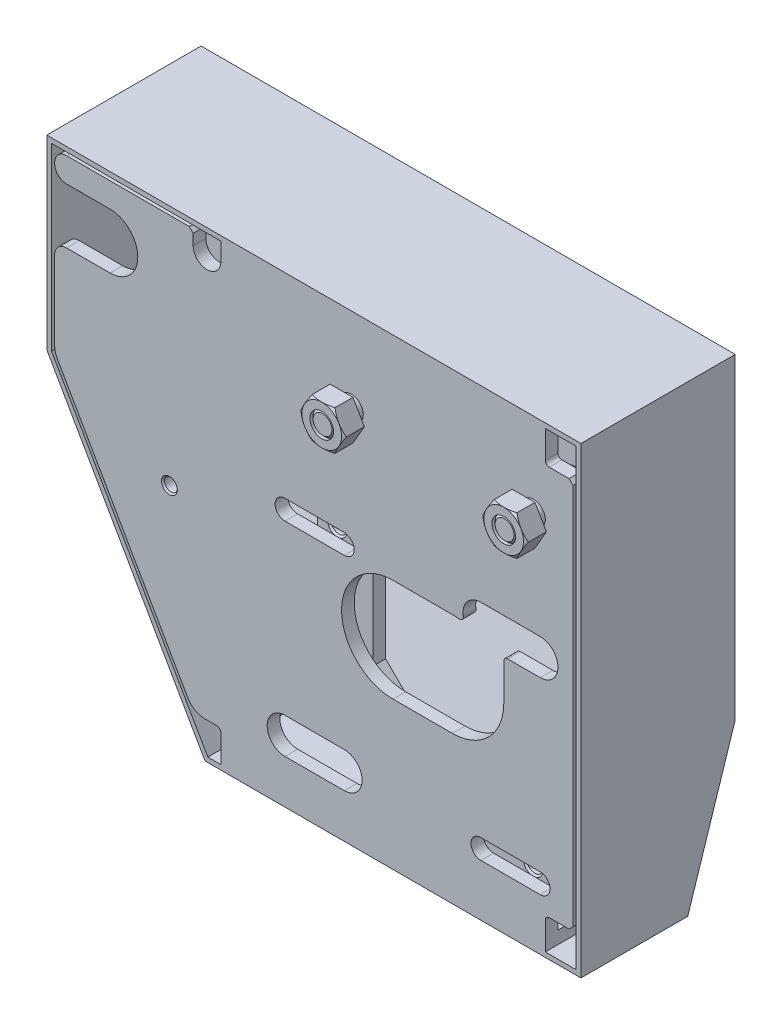
SolidWorks part; units mm, degrees
ref_plane "前视基准面" through (0, 0, 0) normal (0, 0, 1) x (1, 0, 0)
ref_plane "上视基准面" through (0, 0, 0) normal (0, 1, 0) x (1, 0, 0)
ref_plane "右视基准面" through (0, 0, 0) normal (1, 0, 0) x (0, 0, -1)
ref_plane "基准面4" through (0, 0, 0) normal (0, 0, 1) x (1, 0, 0)
sketch "草图1" plane through (0, 0, 0) normal (0, 0, 1) x (1, 0, 0)
  line L0 (-16, 15.2) -> (-16, -101.8)
  line L1 (-16, -101.8) -> (119, -101.8)
  line L2 (119, -101.8) -> (119, 15.2)
  line L3 (119, 15.2) -> (-16, 15.2)
extrude "凸台-拉伸1" add sketch "草图1" against normal blind 39
sketch "草图2" plane through (0, 0, 0) normal (0, 0, 1) x (1, 0, 0)
  line L0 (-14.8, 14) -> (-14.8, -31.4813)
  line L1 (-14.8, -31.4813) -> (24.6964, -100.6)
  line L2 (24.6964, -100.6) -> (117.8, -100.6)
  line L3 (117.8, -100.6) -> (117.8, 14)
  line L4 (117.8, 14) -> (-14.8, 14)
extrude "切除-拉伸1" cut sketch "草图2" against normal blind 37.8
ref_plane "基准面5" through (-16, 0, 0) normal (1, 0, 0) x (0, 0, -1)
sketch "草图3" plane through (-16, 0, 0) normal (1, 0, 0) x (0, 0, -1)
  line L0 (25.7385, -101.8) -> (39, -101.8)
  line L1 (39, -101.8) -> (39, -60.9103)
  line L2 (39, -60.9103) -> (25.7385, -101.8)
extrude "凸台-拉伸2" add sketch "草图3" along normal blind 135
sketch "草图4" plane through (-16, 0, 0) normal (1, 0, 0) x (0, 0, -1)
  line L0 (27, -101.8) -> (39, -101.8)
  line L1 (39, -101.8) -> (39, -64.8)
  line L2 (39, -64.8) -> (27, -101.8)
extrude "切除-拉伸2" cut sketch "草图4" along normal blind 135
ref_plane "基准面6" through (0, 0, 0) normal (0, 0, 1) x (1, 0, 0)
sketch "草图5" plane through (0, 0, 0) normal (0, 0, 1) x (1, 0, 0)
  line L0 (-16, -101.8) -> (24, -101.8)
  line L1 (24, -101.8) -> (-16, -31.8)
  line L2 (-16, -31.8) -> (-16, -101.8)
extrude "切除-拉伸3" cut sketch "草图5" against normal blind 39
ref_plane "基准面7" through (28, 0, 0) normal (1, 0, 0) x (0, 0, -1)
sketch "草图6" plane through (28, 0, 0) normal (1, 0, 0) x (0, 0, -1)
  line L0 (0, 14) -> (0, -100.6)
  line L1 (0, -100.6) -> (18, -100.6)
  line L2 (18, -100.6) -> (18, -97.4)
  line L3 (18, -97.4) -> (3.2, -97.4)
  line L4 (3.2, -97.4) -> (3.2, 10.8)
  line L5 (3.2, 10.8) -> (18, 10.8)
  line L6 (18, 10.8) -> (18, 14)
  line L7 (18, 14) -> (0, 14)
extrude "凸台-拉伸3" add sketch "草图6" along normal blind 82
ref_plane "基准面8" through (0, 0, 0) normal (0, 0, 1) x (1, 0, 0)
sketch "草图7" plane through (0, 0, 0) normal (0, 0, 1) x (1, 0, 0)
  line L0 (-13.3412, -32.4217) -> (19.6068, -90.0807)
  line L1 (23.948, -92.6) -> (27, -92.6)
  line L2 (28, -93.6) -> (28, -100.6)
  line L3 (28, -100.6) -> (110, -100.6)
  line L4 (110, -100.6) -> (110, -93.6)
  line L5 (111, -92.6) -> (116, -92.6)
  line L6 (116, -92.6) -> (117, -91.6)
  line L7 (117, -91.6) -> (117, 5)
  line L8 (117, 5) -> (116, 6)
  line L9 (116, 6) -> (111, 6)
  line L10 (110, 7) -> (110, 14)
  line L11 (110, 14) -> (28, 14)
  line L12 (28, 14) -> (28, 9.5)
  line L13 (21, 9.5) -> (21, 12.2)
  line L14 (21, 12.2) -> (20, 13.2)
  line L15 (20, 13.2) -> (-11, 13.2)
  line L16 (-14, 10.2) -> (-14, 10)
  line L17 (-11, 7) -> (0, 7)
  line L18 (0, -7) -> (-11, -7)
  line L19 (-14, -10) -> (-14, -29.941)
  arc A0 (-14, -29.941) -> (-13.3412, -32.4217) centre (-9, -29.941) ccw
  arc A1 (19.6068, -90.0807) -> (23.948, -92.6) centre (23.948, -87.6) ccw
  arc A2 (27, -92.6) -> (28, -93.6) centre (27, -93.6) cw
  arc A3 (110, -93.6) -> (111, -92.6) centre (111, -93.6) cw
  arc A4 (111, 6) -> (110, 7) centre (111, 7) cw
  arc A5 (28, 9.5) -> (21, 9.5) centre (24.5, 9.5) cw
  arc A6 (-11, 13.2) -> (-14, 10.2) centre (-11, 10.2) ccw
  arc A7 (-14, 10) -> (-11, 7) centre (-11, 10) ccw
  arc A8 (0, 7) -> (0, -7) centre (0, 0) cw
  arc A9 (-11, -7) -> (-14, -10) centre (-11, -10) ccw
extrude "凸台-拉伸4" add sketch "草图7" against normal blind 3.2
ref_plane "基准面9" through (0, 0, 0) normal (0, 0, 1) x (1, 0, 0)
sketch "草图8" plane through (0, 0, 0) normal (0, 0, 1) x (1, 0, 0)
  line L0 (71.5, -64.5) -> (86.5, -64.5)
  line L1 (99.5, -51.5) -> (99.5, -42.2)
  line L2 (100.5, -41.2) -> (108.7, -41.2)
  line L3 (108.7, -32.2) -> (93.7, -32.2)
  line L4 (86.5, -38.5) -> (71.5, -38.5)
  arc A0 (71.5, -38.5) -> (71.5, -64.5) centre (71.5, -51.5) ccw
  arc A1 (86.5, -64.5) -> (99.5, -51.5) centre (86.5, -51.5) ccw
  arc A2 (99.5, -42.2) -> (100.5, -41.2) centre (100.5, -42.2) cw
  arc A3 (108.7, -41.2) -> (108.7, -32.2) centre (108.7, -36.7) ccw
  arc A4 (93.7, -32.2) -> (89.2625, -37.4471) centre (93.7, -36.7) ccw
  arc A5 (89.2625, -37.4471) -> (88.1495, -38.6051) centre (88.2763, -37.6131) cw
  arc A6 (88.1495, -38.6051) -> (86.5, -38.5) centre (86.5, -51.5) ccw
extrude "切除-拉伸4" cut sketch "草图8" against normal blind 3.2
sketch "草图9" plane through (0, 0, 0) normal (0, 0, 1) x (1, 0, 0)
  line L0 (44.2, -90.7) -> (59.2, -90.7)
  line L1 (59.2, -81.7) -> (44.2, -81.7)
  arc A0 (44.2, -81.7) -> (44.2, -90.7) centre (44.2, -86.2) ccw
  arc A1 (59.2, -90.7) -> (59.2, -81.7) centre (59.2, -86.2) ccw
extrude "切除-拉伸5" cut sketch "草图9" against normal blind 3.2
sketch "草图10" plane through (0, 0, 0) normal (0, 0, 1) x (1, 0, 0)
  line L0 (44.2, -39.2) -> (59.2, -39.2)
  line L1 (59.2, -34.2) -> (44.2, -34.2)
  arc A0 (44.2, -34.2) -> (44.2, -39.2) centre (44.2, -36.7) ccw
  arc A1 (59.2, -39.2) -> (59.2, -34.2) centre (59.2, -36.7) ccw
extrude "切除-拉伸6" cut sketch "草图10" against normal blind 3.2
sketch "草图11" plane through (0, 0, 0) normal (0, 0, 1) x (1, 0, 0)
  line L0 (93.7, -88.7) -> (108.7, -88.7)
  line L1 (108.7, -83.7) -> (93.7, -83.7)
  arc A0 (93.7, -83.7) -> (93.7, -88.7) centre (93.7, -86.2) ccw
  arc A1 (108.7, -88.7) -> (108.7, -83.7) centre (108.7, -86.2) ccw
extrude "切除-拉伸7" cut sketch "草图11" against normal blind 3.2
ref_plane "基准面10" through (15, 0, 0) normal (1, 0, 0) x (0, 0, -1)
sketch "草图12" plane through (15, 0, 0) normal (1, 0, 0) x (0, 0, -1)
  line L0 (0, -46) -> (0, -44)
  line L1 (0, -44) -> (0.379, -44.379)
  line L2 (0.379, -44.379) -> (2.821, -44.379)
  line L3 (2.821, -44.379) -> (3.2, -44)
  line L4 (3.2, -44) -> (3.2, -46)
  line L5 (3.2, -46) -> (0, -46)
  line L6 (3.2, -46) -> (0, -46) construction
revolve "切除-旋转1" cut sketch "草图12" angle 360 about L6 reverse direction yes
cosmetic thread "装饰螺纹线1" parameters "D1"=3.2, "D2"=4
ref_plane "基准面11" through (0, -6, 0) normal (0, 1, 0) x (1, 0, 0)
sketch "草图13" plane through (0, -6, 0) normal (0, 1, 0) x (1, 0, 0)
  line L0 (61, 10.7) -> (65.7, 10.7)
  line L1 (65.7, 10.7) -> (66, 10.4)
  line L2 (66, 10.4) -> (66, 4.7)
  line L3 (66, 4.7) -> (67.1, 4.7)
  line L4 (67.1, 4.7) -> (67.1, 3.2)
  line L5 (67.1, 3.2) -> (64, 3.2)
  line L6 (64, 3.2) -> (64, -2.5)
  line L7 (64, -2.5) -> (74.6603, -2.5)
  line L8 (74.6603, -2.5) -> (66, -7.5)
  line L9 (66, -7.5) -> (64, -7.5)
  line L10 (64, -7.5) -> (64, -6.6865)
  line L11 (64, -6.6865) -> (63.3865, -7.3)
  line L12 (63.3865, -7.3) -> (61, -7.3)
  line L13 (61, -7.3) -> (61, 10.7)
  line L14 (61, -7.3) -> (61, 10.7) construction
revolve "旋转1" add sketch "草图13" angle 360 about L14 reverse direction yes
cosmetic thread "装饰螺纹线2" parameters "D1"=7.5, "D2"=4.773
ref_plane "基准面12" through (0, 0, 7.5) normal (0, 0, 1) x (1, 0, 0)
sketch "草图14" plane through (0, 0, 7.5) normal (0, 0, 1) x (1, 0, 0)
  line L0 (55.2265, -6) -> (58.1132, -11)
  line L1 (58.1132, -11) -> (63.8868, -11)
  line L2 (63.8868, -11) -> (66.7735, -6)
  line L3 (66.7735, -6) -> (63.8868, -1)
  line L4 (63.8868, -1) -> (58.1132, -1)
  line L5 (58.1132, -1) -> (55.2265, -6)
  circle A0 centre (61, -6) radius 20
extrude "切除-拉伸8" cut sketch "草图14" against normal blind 5
ref_plane "基准面13" through (0, 0, -10.7) normal (0, 0, -1) x (-1, 0, 0)
sketch "草图15" plane through (0, 0, -10.7) normal (0, 0, -1) x (-1, 0, 0)
  line L0 (-58.5, -7.4434) -> (-58.5, -4.5566)
  line L1 (-58.5, -4.5566) -> (-61, -3.1132)
  line L2 (-61, -3.1132) -> (-63.5, -4.5566)
  line L3 (-63.5, -4.5566) -> (-63.5, -7.4434)
  line L4 (-63.5, -7.4434) -> (-61, -8.8868)
  line L5 (-61, -8.8868) -> (-58.5, -7.4434)
extrude "切除-拉伸9" cut sketch "草图15" against normal blind 2
sketch "草图16" plane through (0, -6, 0) normal (0, 1, 0) x (1, 0, 0)
  line L0 (107, 10.7) -> (111.7, 10.7)
  line L1 (111.7, 10.7) -> (112, 10.4)
  line L2 (112, 10.4) -> (112, 4.7)
  line L3 (112, 4.7) -> (113.1, 4.7)
  line L4 (113.1, 4.7) -> (113.1, 3.2)
  line L5 (113.1, 3.2) -> (110, 3.2)
  line L6 (110, 3.2) -> (110, -2.5)
  line L7 (110, -2.5) -> (120.6603, -2.5)
  line L8 (120.6603, -2.5) -> (112, -7.5)
  line L9 (112, -7.5) -> (110, -7.5)
  line L10 (110, -7.5) -> (110, -6.6865)
  line L11 (110, -6.6865) -> (109.3865, -7.3)
  line L12 (109.3865, -7.3) -> (107, -7.3)
  line L13 (107, -7.3) -> (107, 10.7)
  line L14 (107, -7.3) -> (107, 10.7) construction
revolve "旋转2" add sketch "草图16" angle 360 about L14 reverse direction yes
cosmetic thread "装饰螺纹线3" parameters "D1"=7.5, "D2"=4.773
ref_plane "基准面14" through (0, 0, 7.5) normal (0, 0, 1) x (1, 0, 0)
sketch "草图17" plane through (0, 0, 7.5) normal (0, 0, 1) x (1, 0, 0)
  line L0 (101.2265, -6) -> (104.1132, -11)
  line L1 (104.1132, -11) -> (109.8868, -11)
  line L2 (109.8868, -11) -> (112.7735, -6)
  line L3 (112.7735, -6) -> (109.8868, -1)
  line L4 (109.8868, -1) -> (104.1132, -1)
  line L5 (104.1132, -1) -> (101.2265, -6)
  circle A0 centre (107, -6) radius 20
extrude "切除-拉伸10" cut sketch "草图17" against normal blind 5
ref_plane "基准面15" through (0, 0, -10.7) normal (0, 0, -1) x (-1, 0, 0)
sketch "草图18" plane through (0, 0, -10.7) normal (0, 0, -1) x (-1, 0, 0)
  line L0 (-104.5, -7.4434) -> (-104.5, -4.5566)
  line L1 (-104.5, -4.5566) -> (-107, -3.1132)
  line L2 (-107, -3.1132) -> (-109.5, -4.5566)
  line L3 (-109.5, -4.5566) -> (-109.5, -7.4434)
  line L4 (-109.5, -7.4434) -> (-107, -8.8868)
  line L5 (-107, -8.8868) -> (-104.5, -7.4434)
extrude "切除-拉伸11" cut sketch "草图18" against normal blind 2
ref_plane "基准面16" through (0, -57.5, 0) normal (0, 1, 0) x (1, 0, 0)
sketch "草图19" plane through (0, -57.5, 0) normal (0, 1, 0) x (1, 0, 0)
  line L0 (12.2, 3.2) -> (32.2, 3.2)
  line L1 (32.2, 3.2) -> (32.2, 21.2)
  line L2 (32.2, 21.2) -> (29, 21.2)
  line L3 (29, 21.2) -> (29, 6.4)
  line L4 (29, 6.4) -> (12.2, 6.4)
  line L5 (12.2, 6.4) -> (12.2, 3.2)
extrude "凸台-拉伸5" add sketch "草图19" against normal blind 20
ref_plane "基准面17" through (29, 0, 0) normal (-1, 0, 0) x (0, 0, 1)
sketch "草图20" plane through (29, 0, 0) normal (-1, 0, 0) x (0, 0, 1)
  line L0 (-23.2, -55.5) -> (-23.2, -79.5)
  line L1 (-23.2, -79.5) -> (-19.2, -79.5)
  line L2 (-19.2, -79.5) -> (-19.2, -77.5)
  line L3 (-19.2, -77.5) -> (-21.2, -75.5)
  line L4 (-21.2, -75.5) -> (-21.2, -59.5)
  line L5 (-21.2, -59.5) -> (-19.2, -57.5)
  line L6 (-19.2, -57.5) -> (-19.2, -55.5)
  line L7 (-19.2, -55.5) -> (-23.2, -55.5)
extrude "切除-拉伸12" cut sketch "草图20" against normal blind 3.2
ref_plane "基准面18" through (0, 0, -6.4) normal (0, 0, -1) x (-1, 0, 0)
sketch "草图21" plane through (0, 0, -6.4) normal (0, 0, -1) x (-1, 0, 0)
  line L0 (-12.2, -57.5) -> (-16.2, -57.5)
  line L1 (-16.2, -57.5) -> (-12.2, -61.5)
  line L2 (-12.2, -61.5) -> (-12.2, -57.5)
extrude "切除-拉伸13" cut sketch "草图21" against normal blind 3.2
ref_plane "基准面19" through (0, 0, -6.4) normal (0, 0, -1) x (-1, 0, 0)
sketch "草图22" plane through (0, 0, -6.4) normal (0, 0, -1) x (-1, 0, 0)
  line L0 (-12.2, -77.5) -> (-12.2, -73.5)
  line L1 (-12.2, -73.5) -> (-16.2, -77.5)
  line L2 (-16.2, -77.5) -> (-12.2, -77.5)
extrude "切除-拉伸14" cut sketch "草图22" against normal blind 3.2
ref_plane "基准面20" through (0, 0, -15.2) normal (0, 0, 1) x (1, 0, 0)
sketch "草图23" plane through (0, 0, -15.2) normal (0, 0, 1) x (1, 0, 0)
  line L0 (14.25, -67.5) -> (14.25, -63.55)
  line L1 (14.25, -63.55) -> (14.55, -63.25)
  line L2 (14.55, -63.25) -> (19.25, -63.25)
  line L3 (19.25, -63.25) -> (19.25, -65)
  line L4 (19.25, -65) -> (43.7595, -65)
  line L5 (43.7595, -65) -> (44.25, -65.4905)
  line L6 (44.25, -65.4905) -> (44.25, -67.5)
  line L7 (44.25, -67.5) -> (14.25, -67.5)
  line L8 (44.25, -67.5) -> (14.25, -67.5) construction
revolve "旋转3" add sketch "草图23" angle 360 about L8 reverse direction yes
cosmetic thread "装饰螺纹线4" parameters "D1"=24, "D2"=4.019
sketch "草图24" plane through (0, 0, -15.2) normal (0, 0, 1) x (1, 0, 0)
  line L0 (25, -67.5) -> (25, -63.5)
  line L1 (25, -63.5) -> (26.1547, -61.5)
  line L2 (26.1547, -61.5) -> (29, -61.5)
  line L3 (29, -61.5) -> (29, -67.5)
  line L4 (29, -67.5) -> (25, -67.5)
  line L5 (29, -67.5) -> (25, -67.5) construction
revolve "旋转4" add sketch "草图24" angle 360 about L5 reverse direction yes
ref_plane "基准面21" through (29, 0, 0) normal (-1, 0, 0) x (0, 0, 1)
sketch "草图25" plane through (29, 0, 0) normal (-1, 0, 0) x (0, 0, 1)
  line L0 (-19.2, -65.1906) -> (-19.2, -69.8094)
  line L1 (-19.2, -69.8094) -> (-15.2, -72.1188)
  line L2 (-15.2, -72.1188) -> (-11.2, -69.8094)
  line L3 (-11.2, -69.8094) -> (-11.2, -65.1906)
  line L4 (-11.2, -65.1906) -> (-15.2, -62.8812)
  line L5 (-15.2, -62.8812) -> (-19.2, -65.1906)
  circle A0 centre (-15.2, -67.5) radius 6
extrude "切除-拉伸15" cut sketch "草图25" along normal blind 4
ref_plane "基准面22" through (0, 0, -3.2) normal (0, 0, 1) x (1, 0, 0)
sketch "草图26" plane through (0, 0, -3.2) normal (0, 0, 1) x (1, 0, 0)
  line L0 (49.25, -33) -> (49.25, -76.5)
  line L1 (49.25, -76.5) -> (56.75, -76.5)
  line L2 (56.75, -76.5) -> (72.25, -92)
  line L3 (72.25, -92) -> (106.75, -92)
  line L4 (106.75, -92) -> (108.75, -90)
  line L5 (108.75, -90) -> (108.75, -80)
  line L6 (108.75, -80) -> (106.75, -78)
  line L7 (106.75, -78) -> (78.25, -78)
  line L8 (78.25, -78) -> (63.25, -63)
  line L9 (63.25, -63) -> (63.25, -33)
  line L10 (63.25, -33) -> (61.25, -31)
  line L11 (61.25, -31) -> (51.25, -31)
  line L12 (51.25, -31) -> (49.25, -33)
extrude "凸台-拉伸6" add sketch "草图26" against normal blind 3.2
ref_plane "基准面23" through (0, -69, 0) normal (0, 1, 0) x (1, 0, 0)
sketch "草图27" plane through (0, -69, 0) normal (0, 1, 0) x (1, 0, 0)
  line L0 (44.25, 21.2) -> (44.25, 8.2)
  line L1 (49.25, 3.2) -> (49.25, 6.4)
  line L2 (47.45, 8.2) -> (47.45, 21.2)
  line L3 (47.45, 21.2) -> (44.25, 21.2)
  arc A0 (44.25, 8.2) -> (49.25, 3.2) centre (49.25, 8.2) ccw
  arc A1 (49.25, 6.4) -> (47.45, 8.2) centre (49.25, 8.2) cw
extrude "凸台-拉伸7" add sketch "草图27" against normal blind 7.5 and the other way blind 7.5
ref_plane "基准面24" through (47.45, 0, 0) normal (1, 0, 0) x (0, 0, -1)
sketch "草图28" plane through (47.45, 0, 0) normal (1, 0, 0) x (0, 0, -1)
  line L0 (23.2, -78.5) -> (23.2, -59.5)
  line L1 (23.2, -59.5) -> (19.2, -59.5)
  line L2 (19.2, -59.5) -> (19.2, -61.5)
  line L3 (19.2, -61.5) -> (21.2, -63.5)
  line L4 (21.2, -63.5) -> (21.2, -74.5)
  line L5 (21.2, -74.5) -> (19.2, -76.5)
  line L6 (19.2, -76.5) -> (19.2, -78.5)
  line L7 (19.2, -78.5) -> (23.2, -78.5)
extrude "切除-拉伸16" cut sketch "草图28" against normal blind 3.2
ref_plane "基准面25" through (54.25, 0, 0) normal (1, 0, 0) x (0, 0, -1)
sketch "草图29" plane through (54.25, 0, 0) normal (1, 0, 0) x (0, 0, -1)
  line L0 (3.2, -36.75) -> (3.2, -34.25)
  line L1 (3.2, -34.25) -> (3.633, -34.683)
  line L2 (3.633, -34.683) -> (5.967, -34.683)
  line L3 (5.967, -34.683) -> (6.4, -34.25)
  line L4 (6.4, -34.25) -> (6.4, -36.75)
  line L5 (6.4, -36.75) -> (3.2, -36.75)
  line L6 (6.4, -36.75) -> (3.2, -36.75) construction
revolve "切除-旋转2" cut sketch "草图29" angle 360 about L6 reverse direction yes
cosmetic thread "装饰螺纹线5" parameters "D1"=3.2, "D2"=5
ref_plane "基准面26" through (103.75, 0, 0) normal (1, 0, 0) x (0, 0, -1)
sketch "草图30" plane through (103.75, 0, 0) normal (1, 0, 0) x (0, 0, -1)
  line L0 (3.2, -86.25) -> (3.2, -83.75)
  line L1 (3.2, -83.75) -> (3.633, -84.183)
  line L2 (3.633, -84.183) -> (5.967, -84.183)
  line L3 (5.967, -84.183) -> (6.4, -83.75)
  line L4 (6.4, -83.75) -> (6.4, -86.25)
  line L5 (6.4, -86.25) -> (3.2, -86.25)
  line L6 (6.4, -86.25) -> (3.2, -86.25) construction
revolve "切除-旋转3" cut sketch "草图30" angle 360 about L6 reverse direction yes
cosmetic thread "装饰螺纹线6" parameters "D1"=3.2, "D2"=5
ref_plane "基准面27" through (0, 0, -12) normal (0, 0, 1) x (1, 0, 0)
sketch "草图31" plane through (0, 0, -12) normal (0, 0, 1) x (1, 0, 0)
  line L0 (36, -101.8) -> (38.75, -101.8)
  line L1 (37.4, -103.45) -> (36, -103.45)
  line L2 (36, -103.45) -> (36, -101.8)
  line L3 (36, -103.45) -> (36, -101.8) construction
  arc A0 (38.75, -101.8) -> (37.4, -103.45) centre (36.7653, -101.5534) cw
revolve "旋转5" add sketch "草图31" angle 360 about L3 reverse direction yes
sketch "草图32" plane through (0, 0, -12) normal (0, 0, 1) x (1, 0, 0)
  line L0 (102, -101.8) -> (104.75, -101.8)
  line L1 (103.4, -103.45) -> (102, -103.45)
  line L2 (102, -103.45) -> (102, -101.8)
  line L3 (102, -103.45) -> (102, -101.8) construction
  arc A0 (104.75, -101.8) -> (103.4, -103.45) centre (102.7653, -101.5534) cw
revolve "旋转6" add sketch "草图32" angle 360 about L3 reverse direction yes
ref_plane "基准面28" through (0, 0, 0) normal (0, 0, 1) x (1, 0, 0)
ref_plane "基准面29" through (0, 0, -8) normal (0, 0, 1) x (1, 0, 0)
ref_plane "to_lane XY" through (0, 0, 0) normal (0, 0, 1) x (1, 0, 0)
ref_plane "to_lane XZ" through (0, 0, 0) normal (0, -1, 0) x (-1, 0, 0)
ref_plane "to_lane YZ" through (0, 0, 0) normal (1, 0, 0) x (0, 0, -1)
ref_axis "to_lane X" through (-80.9, 0, 0) along (1, 0, 0)
ref_axis "to_lane Y" through (0, -50, 0) along (0, 1, 0)
ref_axis "to_lane Z" through (0, 0, 80.9) along (0, 0, -1)
sketch3d "to_lane"
  point P0 (0, 0, 0)
ref_plane "to_motor XY" through (0, 0, 0) normal (0, 0, 1) x (1, 0, 0)
ref_plane "to_motor XZ" through (0, -51.5, 0) normal (0, -1, 0) x (-1, 0, 0)
ref_plane "to_motor YZ" through (79, 0, 0) normal (1, 0, 0) x (0, 0, -1)
ref_axis "to_motor X" through (-80.9, -51.5, 0) along (1, 0, 0)
ref_axis "to_motor Y" through (79, -50, 0) along (0, 1, 0)
ref_axis "to_motor Z" through (79, -51.5, 80.9) along (0, 0, -1)
sketch3d "to_motor"
  point P0 (79, -51.5, 0)
ref_plane "to_capacitor XY" through (0, 0, 0) normal (0, 0, 1) x (1, 0, 0)
ref_plane "to_capacitor XZ" through (0, -46, 0) normal (0, -1, 0) x (-1, 0, 0)
ref_plane "to_capacitor YZ" through (15, 0, 0) normal (1, 0, 0) x (0, 0, -1)
ref_axis "to_capacitor X" through (-80.9, -46, 0) along (1, 0, 0)
ref_axis "to_capacitor Y" through (15, -50, 0) along (0, 1, 0)
ref_axis "to_capacitor Z" through (15, -46, 80.9) along (0, 0, -1)
sketch3d "to_capacitor"
  point P0 (15, -46, 0)
ref_plane "to_transfer_parts XY" through (0, 0, -8) normal (0, 0, -1) x (-1, 0, 0)
ref_plane "to_transfer_parts XZ" through (0, -51.5, 0) normal (0, 1, 0) x (1, 0, 0)
ref_plane "to_transfer_parts YZ" through (79, 0, 0) normal (1, 0, 0) x (0, 0, -1)
ref_axis "to_transfer_parts X" through (-80.9, -51.5, -8) along (1, 0, 0)
ref_axis "to_transfer_parts Y" through (79, 50, -8) along (0, -1, 0)
ref_axis "to_transfer_parts Z" through (79, -51.5, -80.9) along (0, 0, 1)
sketch3d "to_transfer_parts"
  point P0 (79, -51.5, -8)
